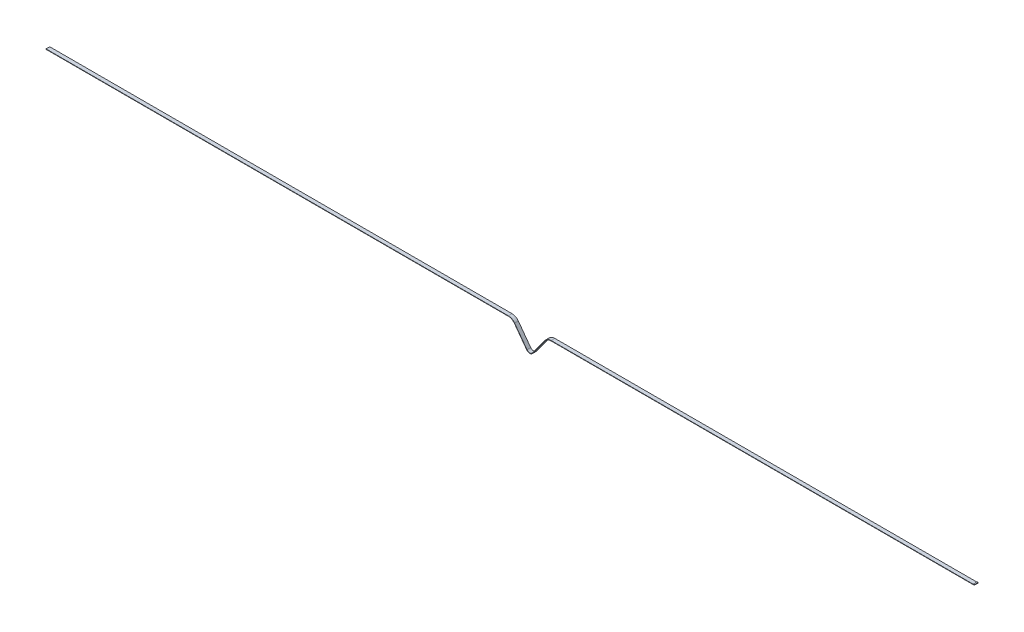
SolidWorks part; units mm, degrees
ref_plane "Front Plane" through (0, 0, 0) normal (0, 0, 1) x (1, 0, 0)
ref_plane "Top Plane" through (0, 0, 0) normal (0, 1, 0) x (1, 0, 0)
ref_plane "Right Plane" through (0, 0, 0) normal (1, 0, 0) x (0, 0, -1)
sketch "Sketch1" plane through (0, 0, 0) normal (1, 0, 0) x (0, 0, -1)
  line L1 (0, 0) -> (6, 0)
  line L2 (0, 0) -> (0, 0.63)
  line L3 (0, 0.63) -> (6, 0.63)
  line L4 (6, 0) -> (6, 0.63)
  dimension "D1" = 0.63
  dimension "D2" = 6
sketch "Sketch2" plane through (0, 0, 0) normal (0, 0, 1) x (1, 0, 0)
  line L0 (0, 0) -> (-683.7729, 0)
  line L1 (-693.4055, -4.8779) -> (-713.4177, -32.1359)
  line L2 (-723.268, -32.1359) -> (-743.2802, -4.8779)
  line L3 (-752.9129, 0) -> (-1500, 0)
  arc A0 (-683.7729, 0) -> (-693.4055, -4.8779) centre (-683.7729, -11.95) ccw
  arc A1 (-713.4177, -32.1359) -> (-723.268, -32.1359) centre (-718.3429, -28.52) cw
  arc A2 (-743.2802, -4.8779) -> (-752.9129, 0) centre (-752.9129, -11.95) ccw
  circle A3 centre (-752.9129, -11.95) radius 11.95 construction
  circle A4 centre (-718.3429, -28.52) radius 6.11 construction
  circle A5 centre (-683.7729, -11.95) radius 11.95 construction
  dimension "D1" = 6.11
  dimension "D4" = 1500
sweep "Sweep1" add profiles "Sketch1" path "Sketch2"
sketch "Sketch3" plane through (0, 0, 0) normal (0, 0, 1) x (1, 0, 0)
  line L0 (0, 0.63) -> (-683.7729, 0.63) construction
  line L1 (-1.5, 0.63) -> (-1.5, 0)
  line L2 (0, 0) -> (-683.7729, 0) construction
  line L3 (-1.5, 0) -> (0, 0)
  line L4 (0, 0) -> (0, 0.63)
  arc A1 (0, 0.63) -> (-1.5, 0.63) centre (-0.75, 0.63) ccw
  dimension "D1" = 0.75
extrude "Boss-Extrude1" add sketch "Sketch3" against normal through all
pattern_curve "CrvPattern1" [suppressed] of bodies 102 driven by "Sketch2" parameters "D1"=2000, "D3"=2, "D2"=1, "D4"=10
